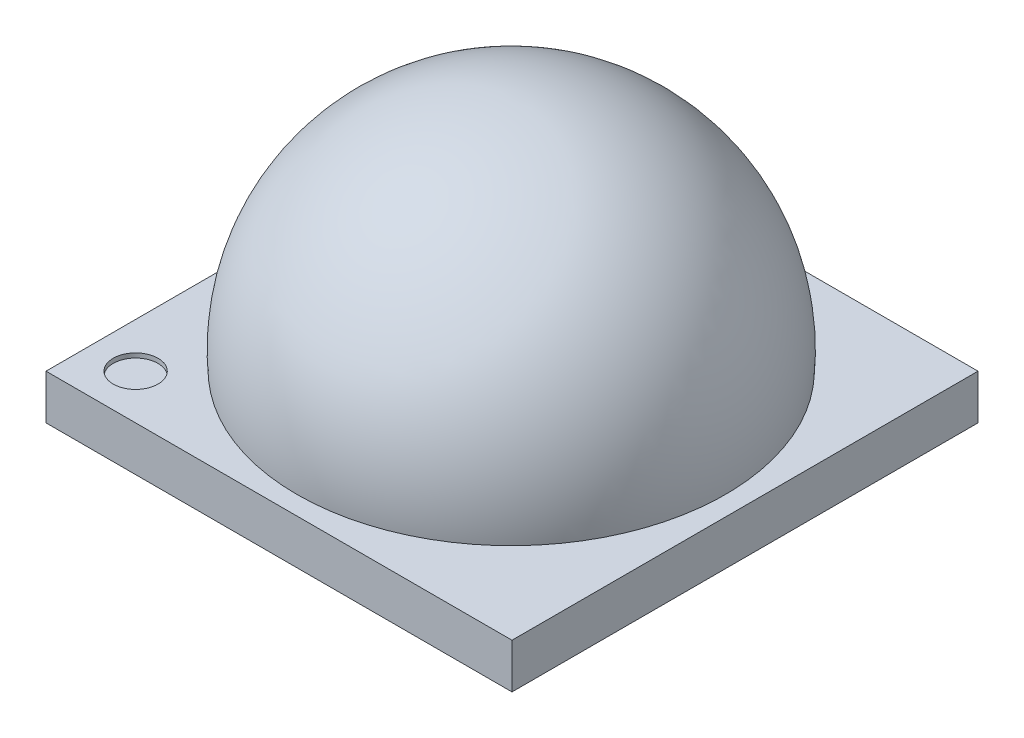
SolidWorks part; units mm, degrees
material "Alliage 2018"
ref_plane "Plan de face" through (0, 0, 0) normal (0, 0, 1) x (1, 0, 0)
ref_plane "Plan de dessus" through (0, 0, 0) normal (0, 1, 0) x (1, 0, 0)
ref_plane "Plan de droite" through (0, 0, 0) normal (1, 0, 0) x (0, 0, -1)
sketch "Esquisse1" plane through (0, 0, 0) normal (0, 1, 0) x (1, 0, 0)
  line L0 (-1.4, 2.45) -> (-0.3, 2.45)
  line L1 (-2.4, 2.45) -> (-1.9, 2.45)
  line L2 (-2.4, 2.45) -> (-2.4, 0.3)
  line L3 (-2.4, -2.45) -> (-1.9, -2.45)
  line L4 (2.4, 2.45) -> (2.4, 0.3)
  line L5 (0.3, 2.45) -> (1.4, 2.45)
  line L6 (-0.3, 2.1) -> (-1.4, 2.1)
  line L7 (1.4, -2.1) -> (0.3, -2.1)
  line L8 (1.9, -2.45) -> (1.9, -0.3)
  line L9 (1.4, 2.1) -> (0.3, 2.1)
  line L10 (-1.9, -2.45) -> (-1.9, -0.3)
  line L11 (1.9, 2.45) -> (2.4, 2.45)
  line L12 (1.4, 2.1) -> (1.4, 2.45)
  line L13 (-1.4, -1.8) -> (1.4, -1.8)
  line L14 (-1.4, -2.45) -> (-1.4, -2.1)
  line L15 (-1.1, 1.8) -> (1.4, 1.8)
  line L16 (1.4, -2.45) -> (1.4, -2.1)
  line L17 (0.3, 2.1) -> (0.3, 2.45)
  line L18 (-0.3, 2.1) -> (-0.3, 2.45)
  line L19 (-2.4, -0.3) -> (-1.9, -0.3)
  line L20 (-2.4, 0.3) -> (-1.9, 0.3)
  line L21 (-1.4, 2.1) -> (-1.4, 2.45)
  line L22 (0.3, -2.45) -> (0.3, -2.1)
  line L23 (-0.3, -2.45) -> (-0.3, -2.1)
  line L24 (1.9, 0.3) -> (2.4, 0.3)
  line L25 (1.9, -0.3) -> (2.4, -0.3)
  line L26 (-0.3, -2.1) -> (-1.4, -2.1)
  line L27 (0.3, -2.45) -> (1.4, -2.45)
  line L28 (-1.4, -2.45) -> (-0.3, -2.45)
  line L29 (-1.4, -1.8) -> (-1.4, 1.5)
  line L30 (1.4, -1.8) -> (1.4, 1.8)
  line L31 (1.9, -2.45) -> (2.4, -2.45)
  line L32 (1.9, 0.3) -> (1.9, 2.45)
  line L33 (2.4, -0.3) -> (2.4, -2.45)
  line L34 (-1.9, 0.3) -> (-1.9, 2.45)
  line L35 (-2.4, -0.3) -> (-2.4, -2.45)
  line L36 (-1.4, 1.5) -> (-1.1, 1.8)
  line L37 (0, 2.6) -> (0, -2.6) construction
  line L38 (2.6, -2.6) -> (-2.6, -2.6)
  line L39 (2.6, -2.6) -> (2.6, 2.6)
  line L40 (2.6, 2.6) -> (-2.6, 2.6)
  line L41 (-2.6, -2.6) -> (-2.6, 2.6)
  line L43 (2.6, 0) -> (-2.6, 0) construction
  circle A0 centre (0, 0) radius 2.4009 construction
  point P0 (0, 0)
  point P6 (0, 0)
  point P11 (0, 0)
  point P14 (0, 0)
  point P19 (0, 0)
  point P26 (0, 0)
  point P52 (0, 0)
  point P55 (0, 0)
  point P56 (0, 0)
  point P57 (0, 0)
  dimension "D3" = 5.2
  dimension "D4" = 5.2
extrude "Boss.-Extru.1" add sketch "Esquisse1" along normal blind 0.5 contours L41 L40 L39 L38
extrude "Boss.-Extru.2" add sketch "Esquisse1<3>" against normal blind 0.025 contours L17 L9 L12 L5 | L21 L6 L18 L0 | L20 L34 L1 L2 | L19 L35 L3 L10 | L14 L28 L23 L26 | L22 L27 L16 L7 | L36 L29 L13 L30 L15 | L32 L11 L4 L24 | L33 L31 L8 L25 region at (-0.85, 0, -2.275) region at (-2.15, 0, -1.375) region at (-2.15, 0, 1.375) region at (0.85, 0, -2.275) region at (0.85, 0, 2.275) region at (0.0058, 0, 0.0076) region at (-0.85, 0, 2.275)
sketch "Esquisse1<3>" plane through (0, 0, 0) normal (0, 1, 0) x (1, 0, 0) same geometry as "Esquisse1"
sketch "Esquisse3" plane through (0, 0, 0) normal (0, 0, 1) x (1, 0, 0)
  line L0 (0, 0) -> (-2.6, 0) construction
  line L3 (2.6, 0.5) -> (-2.6, 0.5) construction
  line L4 (0, 3.1) -> (-0.0001, 3.075)
  line L5 (-2.4, 0.5) -> (-2.3751, 0.5)
  line L6 (-2.3751, 0.5) -> (-2.3751, 0.5021)
  arc A0 (-2.4, 0.5) -> (0, 3.1) centre (-0.0083, 0.7) cw
  arc A1 (-2.3751, 0.5021) -> (-0.0001, 3.075) centre (-0.0083, 0.7) cw
  point P4 (0, 0)
  dimension "D1" = 3.1
  dimension "D2" = 2.4
  dimension "D4" = 0.025
sketch "Esquisse4" plane through (0, 0.5, 0) normal (0, 1, 0) x (1, 0, 0)
  line L0 (0, 2.6) -> (0, 0) construction
  line L1 (2.6, 2.6) -> (-2.6, 2.6) construction
  line L2 (0, 0) -> (-2.6, 0) construction
  line L3 (-2.6, -2.6) -> (-2.6, 2.6) construction
  line L4 (-0.25, 1.125) -> (-0.15, 1.125)
  line L5 (-0.25, 0.25) -> (-1.5, 0.25)
  line L6 (-0.25, 0.25) -> (-0.25, 0.625)
  line L7 (-0.25, 1.5) -> (-1.5, 1.5)
  line L8 (-1.5, 0.25) -> (-1.5, 1.5)
  line L9 (-1.4, 1.4) -> (-1.1, 1.4)
  line L10 (-1.4, 1.4) -> (-1.4, 0.35)
  line L11 (-1.4, 0.35) -> (-1.1, 0.35)
  line L12 (-1.1, 1.4) -> (-1.1, 0.35)
  line L13 (-1.0401, 1.4) -> (-0.7401, 1.4)
  line L14 (-1.0401, 1.4) -> (-1.0401, 0.35)
  line L15 (-1.0401, 0.35) -> (-0.7401, 0.35)
  line L16 (-0.7401, 1.4) -> (-0.7401, 0.35)
  line L17 (-0.65, 1.4) -> (-0.35, 1.4)
  line L18 (-0.65, 1.4) -> (-0.65, 0.35)
  line L19 (-0.65, 0.35) -> (-0.35, 0.35)
  line L20 (-0.35, 1.4) -> (-0.35, 0.35)
  line L21 (-0.25, 0.625) -> (-0.15, 0.625)
  line L22 (-0.875, 1.5) -> (-0.875, 0.875) construction
  line L23 (-0.25, 1.125) -> (-0.25, 1.5)
  line L24 (-0.15, 0.625) -> (-0.15, 1.125)
  line L25 (0.875, 1.5) -> (0.875, 0.875) construction
  line L26 (0.875, -1.5) -> (0.875, -0.875) construction
  line L27 (1.4, 1.4) -> (1.4, 1.1)
  line L28 (1.125, 0.25) -> (1.125, 0.15)
  line L29 (0.25, 0.25) -> (0.25, 1.5)
  line L30 (0.25, 0.25) -> (0.625, 0.25)
  line L31 (1.5, 0.25) -> (1.5, 1.5)
  line L32 (0.25, 1.5) -> (1.5, 1.5)
  line L33 (1.4, 1.4) -> (0.35, 1.4)
  line L34 (0.35, 1.4) -> (0.35, 1.1)
  line L35 (1.4, 1.1) -> (0.35, 1.1)
  line L36 (1.4, 1.0401) -> (1.4, 0.7401)
  line L37 (1.4, 1.0401) -> (0.35, 1.0401)
  line L38 (0.35, 1.0401) -> (0.35, 0.7401)
  line L39 (1.4, 0.7401) -> (0.35, 0.7401)
  line L40 (1.4, 0.65) -> (1.4, 0.35)
  line L41 (1.4, 0.65) -> (0.35, 0.65)
  line L42 (0.35, 0.65) -> (0.35, 0.35)
  line L43 (1.4, 0.35) -> (0.35, 0.35)
  line L44 (1.45, 0.3) -> (1.45, 1.45)
  line L45 (0.625, 0.25) -> (0.625, 0.15)
  line L46 (1.5, 0.875) -> (0.875, 0.875) construction
  line L47 (1.125, 0.25) -> (1.5, 0.25)
  line L48 (0.625, 0.15) -> (1.125, 0.15)
  line L49 (-1.125, -0.25) -> (-1.125, -0.15)
  line L50 (-0.25, -0.25) -> (-0.25, -1.5)
  line L51 (-0.25, -0.25) -> (-0.625, -0.25)
  line L52 (-1.5, -0.25) -> (-1.5, -1.5)
  line L53 (-0.25, -1.5) -> (-1.5, -1.5)
  line L54 (1.45, 0.3) -> (0.3, 0.3)
  line L55 (0.3, 0.3) -> (0.3, 1.45)
  line L56 (1.45, 1.45) -> (0.3, 1.45)
  line L57 (1.45, 0.3) -> (0.3, 1.45) construction
  line L58 (0.3, 0.3) -> (1.45, 1.45) construction
  line L59 (1.4, -1.4) -> (1.1, -1.4)
  line L60 (1.4, -1.4) -> (1.4, -0.35)
  line L61 (1.4, -0.35) -> (1.1, -0.35)
  line L62 (1.1, -1.4) -> (1.1, -0.35)
  line L63 (1.0401, -1.4) -> (0.7401, -1.4)
  line L64 (1.0401, -1.4) -> (1.0401, -0.35)
  line L65 (1.0401, -0.35) -> (0.7401, -0.35)
  line L66 (-0.625, -0.25) -> (-0.625, -0.15)
  line L67 (-1.5, -0.875) -> (-0.875, -0.875) construction
  line L68 (-1.125, -0.25) -> (-1.5, -0.25)
  line L69 (-0.625, -0.15) -> (-1.125, -0.15)
  line L70 (0.25, -1.125) -> (0.15, -1.125)
  line L71 (0.25, -0.25) -> (1.5, -0.25)
  line L72 (0.25, -0.25) -> (0.25, -0.625)
  line L73 (0.25, -1.5) -> (1.5, -1.5)
  line L74 (1.5, -0.25) -> (1.5, -1.5)
  line L75 (0.7401, -1.4) -> (0.7401, -0.35)
  line L76 (0.65, -1.4) -> (0.35, -1.4)
  line L77 (0.65, -1.4) -> (0.65, -0.35)
  line L78 (0.65, -0.35) -> (0.35, -0.35)
  line L79 (0.35, -1.4) -> (0.35, -0.35)
  line L80 (0.3, -1.45) -> (1.45, -1.45)
  line L81 (0.3, -1.45) -> (0.3, -0.3)
  line L82 (0.3, -0.3) -> (1.45, -0.3)
  line L83 (1.45, -1.45) -> (1.45, -0.3)
  line L84 (0.3, -1.45) -> (1.45, -0.3) construction
  line L85 (0.3, -0.3) -> (1.45, -1.45) construction
  line L86 (-1.4, -1.4) -> (-1.4, -1.1)
  line L87 (0.25, -0.625) -> (0.15, -0.625)
  line L88 (0.875, -1.5) -> (0.875, -0.875) construction
  line L89 (0.25, -1.125) -> (0.25, -1.5)
  line L90 (0.15, -0.625) -> (0.15, -1.125)
  line L91 (-1.4, -1.4) -> (-0.35, -1.4)
  line L92 (-0.3, 1.45) -> (-1.45, 1.45)
  line L93 (-0.3, 1.45) -> (-0.3, 0.3)
  line L94 (-0.3, 0.3) -> (-1.45, 0.3)
  line L95 (-1.45, 1.45) -> (-1.45, 0.3)
  line L96 (-0.3, 1.45) -> (-1.45, 0.3) construction
  line L97 (-0.3, 0.3) -> (-1.45, 1.45) construction
  line L98 (-0.35, -1.4) -> (-0.35, -1.1)
  line L99 (-1.4, -1.1) -> (-0.35, -1.1)
  line L100 (-1.4, -1.0401) -> (-1.4, -0.7401)
  line L101 (-1.4, -1.0401) -> (-0.35, -1.0401)
  line L102 (-0.35, -1.0401) -> (-0.35, -0.7401)
  line L103 (-1.4, -0.7401) -> (-0.35, -0.7401)
  line L104 (-1.4, -0.65) -> (-1.4, -0.35)
  line L105 (-1.4, -0.65) -> (-0.35, -0.65)
  line L106 (-0.35, -0.65) -> (-0.35, -0.35)
  line L107 (-1.4, -0.35) -> (-0.35, -0.35)
  line L108 (-1.45, -0.3) -> (-1.45, -1.45)
  line L109 (-1.45, -0.3) -> (-0.3, -0.3)
  line L110 (-0.3, -0.3) -> (-0.3, -1.45)
  line L111 (-1.45, -1.45) -> (-0.3, -1.45)
  line L112 (-1.45, -0.3) -> (-0.3, -1.45) construction
  line L113 (-0.3, -0.3) -> (-1.45, -1.45) construction
  point P26 (-0.25, 0.875)
  point P57 (0.875, 0.25)
  point P82 (-0.875, -0.25)
  point P107 (0.25, -0.875)
  point P123 (0, 0)
  dimension "D1" = 0.25
  dimension "D3" = 1.25
  dimension "D4" = 1.25
  dimension "D5" = 0.1
  dimension "D7" = 0.1
  dimension "D8" = 0.1
  dimension "D9" = 0.1
  dimension "D10" = 0.3
  dimension "D11" = 0.3
  dimension "D12" = 0.3
  dimension "D13" = 0.1
  dimension "D14" = 0.1
  dimension "D15" = 0.1
  dimension "D16" = 0.5
  dimension "D17" = 0.1
  dimension "D18" = 1.25
  dimension "D19" = 1.25
  dimension "D20" = 4
  dimension "D21" = 0.1
  dimension "D31" = 0.5
  dimension "D32" = 0.1
  dimension "D33" = 1.25
  dimension "D34" = 1.25
  dimension "D36" = 0.05
  dimension "D46" = 0.5
  dimension "D47" = 0.1
  dimension "D48" = 1.25
  dimension "D49" = 1.25
  dimension "D61" = 0.5
  dimension "D62" = 0.1
  dimension "D63" = 0.05
extrude "Boss.-Extru.3" add sketch "Esquisse4" along normal blind 0.025 contours L5 L8 L7 L23 L4 L24 L21 L6 | L30 L45 L48 L28 L47 L31 L32 L29 | L71 L74 L73 L89 L70 L90 L87 L72 | L50 L53 L52 L68 L49 L69 L66 L51
extrude "Boss.-Extru.4" add sketch "Esquisse4<3>" along normal blind 0.1 contours L94 L95 L92 L93 | L54 L55 L56 L44 | L111 L110 L109 L108 | L80 L83 L82 L81
sketch "Esquisse4<3>" plane through (0, 0.5, 0) normal (0, 1, 0) x (1, 0, 0) same geometry as "Esquisse4"
extrude "Boss.-Extru.5" add sketch "Esquisse4<4>" along normal blind 0.105 contours L16 L13 L14 L15 | L20 L17 L18 L19 | L35 L27 L33 L34 | L39 L36 L37 L38 | L43 L40 L41 L42 | L79 L76 L77 L78 | L75 L63 L64 L65 | L62 L59 L60 L61 | L107 L104 L105 L106 | L103 L100 L101 L102 | L99 L86 L91 L98 | L12 L11 L10 L9 region at (-0.8901, 0.5, -0.875) region at (-0.5, 0.5, -0.875) region at (0.875, 0.5, -1.25) region at (0.875, 0.5, -0.8901) region at (0.875, 0.5, -0.5) region at (1.25, 0.5, 0.875) region at (0.8901, 0.5, 0.875) region at (0.5, 0.5, 0.875) region at (-0.875, 0.5, 1.25) region at (-0.875, 0.5, 0.8901) region at (-0.875, 0.5, 0.5)
sketch "Esquisse4<4>" plane through (0, 0.5, 0) normal (0, 1, 0) x (1, 0, 0) same geometry as "Esquisse4"
sketch "Esquisse5" plane through (0, 0.525, 0) normal (0, 1, 0) x (1, 0, 0)
  line L0 (-0.15, 0.875) -> (-0.2, 0.875) construction
  line L1 (-0.15, 0.625) -> (-0.15, 1.125) construction
  line L3 (-0.2, 0.875) -> (-0.2, 1.075) construction
  circle A0 centre (-0.2, 1.075) radius 0.025
  dimension "D1" = 0.05
  dimension "D2" = 0.2
  dimension "D3" = 0.05
sketch "Esquisse6" plane through (0, 0.605, 0) normal (0, 1, 0) x (1, 0, 0)
  line L0 (0.35, 1.25) -> (0.4, 1.25) construction
  line L1 (0.35, 1.4) -> (0.35, 1.1) construction
  line L2 (0.35, 0.5) -> (0.4, 0.5) construction
  line L3 (0.35, 0.65) -> (0.35, 0.35) construction
  dimension "D1" = 0.05
ref_plane "Plan1" through (-0.3046, 0, -1.0445) normal (-0.28, 0, -0.96) x (-0.96, 0, 0.28)
sketch "Esquisse7" plane through (-0.3046, 0, -1.0445) normal (-0.28, 0, -0.96) x (-0.96, 0, 0.28)
sketch "Esquisse9" plane through (-0.3046, 0, -1.0445) normal (-0.28, 0, -0.96) x (-0.96, 0, 0.28)
  arc A0 (-0.109, 0.525) -> (-0.734, 0.605) centre (-0.4272, 0.5207) ccw
sweep "Balayage1" add profiles "Esquisse5" path "Esquisse9"
sketch "Esquisse10" plane through (0, 0.525, 0) normal (0, 1, 0) x (1, 0, 0)
  line L2 (-0.15, 0.625) -> (-0.15, 1.125) construction
  circle A0 centre (-0.2, 0.675) radius 0.025
  point P2 (-0.2011, 0.6809)
  point P3 (0, 0)
  point P6 (-0.2029, 0.725)
  point P8 (0, 0)
  dimension "D1" = 0.05
  dimension "D3" = 0.05
  dimension "D2" = 0.2
ref_plane "Plan2" through (0.1658, 0, -0.5683) normal (0.28, 0, -0.96) x (-0.96, 0, -0.28)
sketch "Esquisse11" plane through (0.1658, 0, -0.5683) normal (0.28, 0, -0.96) x (-0.96, 0, -0.28)
  arc A0 (0.3809, 0.5248) -> (-0.2441, 0.6048) centre (0.0627, 0.5205) ccw
sweep "Balayage2" add profiles "Esquisse10" path "Esquisse11"
revolve "Révolution2" add sketch "Esquisse3" angle 360 about L4
sketch "Esquisse12" plane through (0, 0.5, 0) normal (0, 1, 0) x (1, 0, 0)
  line L0 (-2.6, -2.6) -> (-2.1, -2.1) construction
  line L2 (-2.6, -2.6) -> (-2.6, 2.6) construction
  line L3 (2.6, -2.6) -> (-2.6, -2.6) construction
  circle A0 centre (-2.1, -2.1) radius 0.25
  dimension "D3" = 0.5
  dimension "D1" = 0.5
  dimension "D2" = 0.5
extrude "Enlèv. mat.-Extru.1" cut sketch "Esquisse12" against normal blind 0.05 contours A0 region at (-2.1, 0.5, 2.1)
